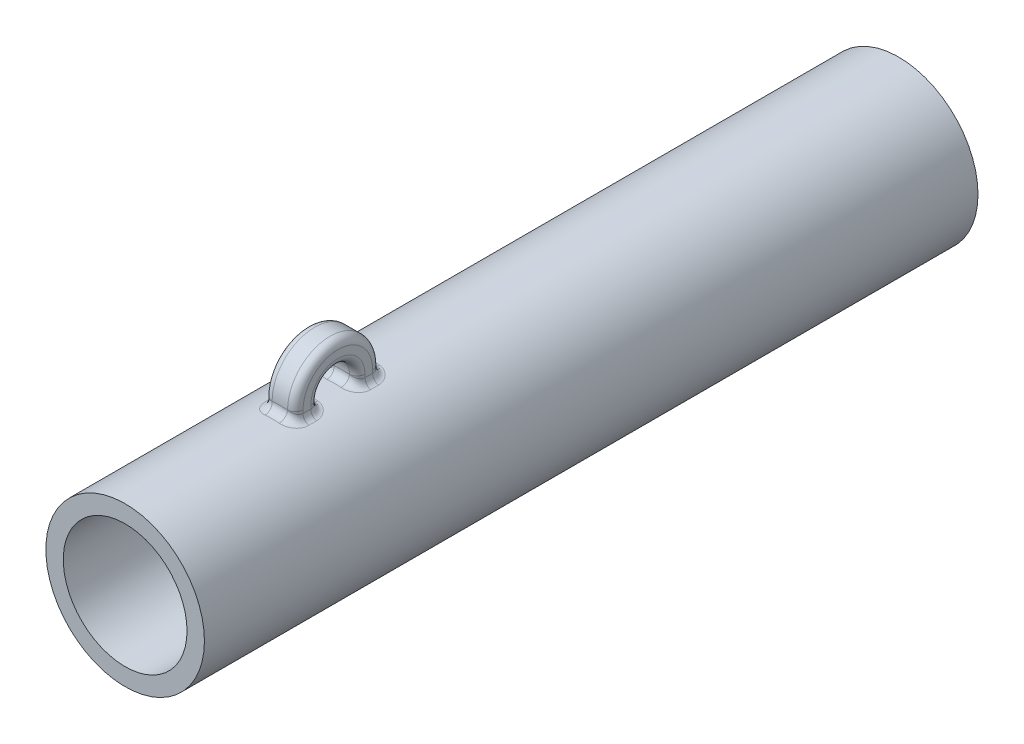
SolidWorks part; units mm, degrees
ref_plane "Front Plane" through (0, 0, 0) normal (0, 0, 1) x (1, 0, 0)
ref_plane "Top Plane" through (0, 0, 0) normal (0, 1, 0) x (1, 0, 0)
ref_plane "Right Plane" through (0, 0, 0) normal (1, 0, 0) x (0, 0, -1)
sketch "Sketch1" plane through (0, 0, 0) normal (0, 0, 1) x (1, 0, 0)
  circle A0 centre (0, 0) radius 8
  circle A1 centre (0, 0) radius 10.25
  dimension "D1" = 16
  dimension "D2" = 20.5
extrude "Boss-Extrude1" add sketch "Sketch1" along normal blind 100
sketch "Sketch3" plane through (0, 0, 0) normal (1, 0, 0) x (0, 0, -1)
  line L0 (-80, 11.25) -> (-80, 8.25)
  line L1 (-80, 8.25) -> (-77, 8.25)
  line L2 (-77, 8.25) -> (-77, 11.25)
  line L3 (-72, 11.25) -> (-72, 8.25)
  line L4 (-72, 8.25) -> (-69, 8.25)
  line L5 (-69, 8.25) -> (-69, 11.25)
  line L6 (0, 10.25) -> (-100, 10.25) construction
  line L7 (-100, 10.25) -> (-100, -10.25) construction
  arc A0 (-69, 11.25) -> (-80, 11.25) centre (-74.5, 11.25) ccw
  arc A1 (-77, 11.25) -> (-72, 11.25) centre (-74.5, 11.25) cw
  dimension "D1" = 3
  dimension "D5" = 3
  dimension "D2" = 2
  dimension "D3" = 20
  dimension "D4" = 5
extrude "Boss-Extrude2" add sketch "Sketch3" along normal blind 2 and the other way blind 2 contours A1 L3 L4 L5 A0 L0 L1 L2
fillet "Fillet1" radius 1 20 edges at (0, 10.25, 72) (0, 10.25, 77) (-2, 10.053, 70.5) (-2, 10.053, 78.5) (2, 10.053, 70.5) (2, 10.053, 78.5) (-2, 10.6515, 77) (-2, 10.6515, 72) (2, 10.6515, 77) (2, 10.6515, 72) (-2, 10.6515, 69) (-2, 10.6515, 80) (2, 10.6515, 69) (2, 10.6515, 80) (0, 10.25, 69) (0, 10.25, 80) (-2, 13.75, 74.5) (2, 13.75, 74.5) (-2, 16.75, 74.5) (2, 16.75, 74.5)
